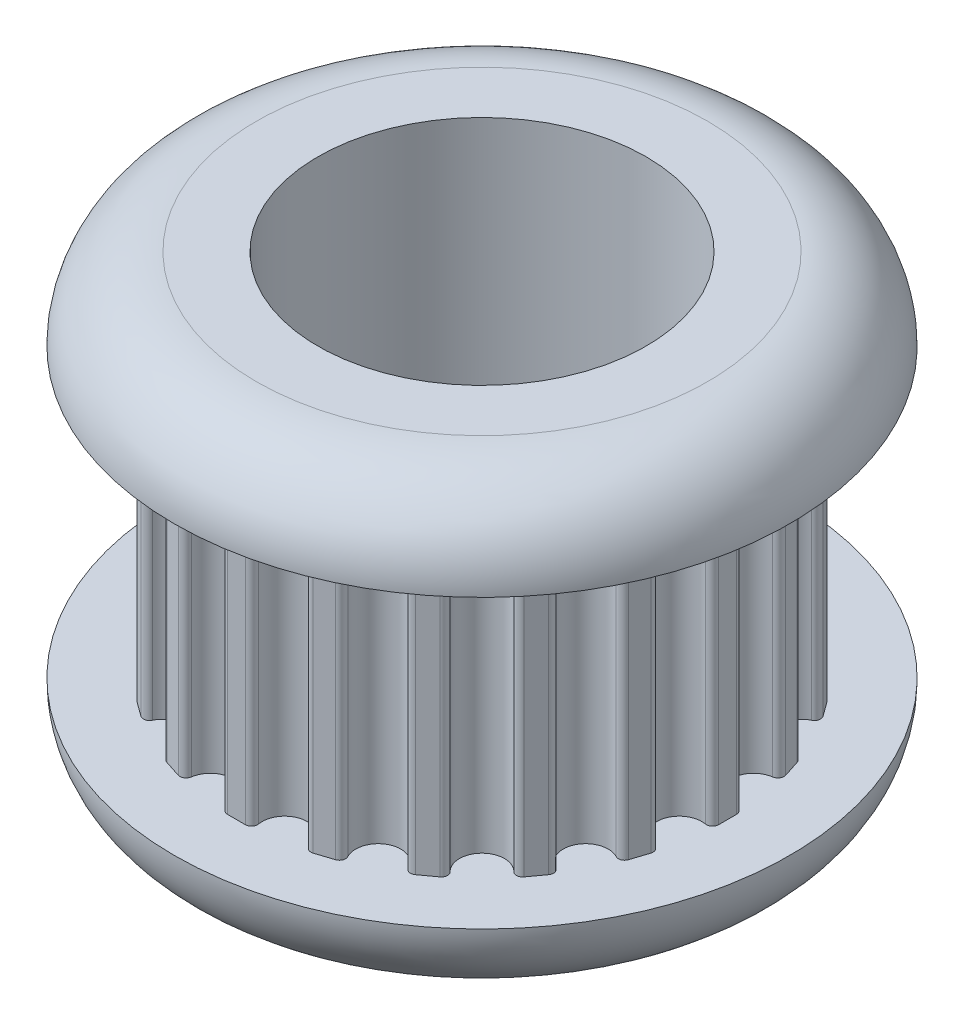
SolidWorks part; units mm, degrees
ref_plane "Front Plane" through (0, 0, 0) normal (0, 0, 1) x (1, 0, 0)
ref_plane "Top Plane" through (0, 0, 0) normal (0, 1, 0) x (1, 0, 0)
ref_plane "Right Plane" through (0, 0, 0) normal (1, 0, 0) x (0, 0, -1)
sketch "Sketch1" plane through (0, 0, 0) normal (0, 1, 0) x (1, 0, 0)
  circle A0 centre (0, 0) radius 6.365
  dimension "D1" = 12.73
extrude "Boss-Extrude2" add sketch "Sketch1" along normal blind 7
sketch "Sketch2" plane through (0, 7, 0) normal (0, 1, 0) x (1, 0, 0)
  line L0 (0, 0) -> (0, 6.365) construction
  line L1 (0, 5.985) -> (0.2155, 5.985)
  line L2 (0, 5.985) -> (0, 6.365)
  line L3 (0, 0) -> (0.905, 5.7138) construction
  line L4 (0, 6.365) -> (0.8189, 6.365)
  line L5 (1.8495, 5.6921) -> (1.6445, 5.7587)
  line L6 (1.8495, 5.6921) -> (1.9669, 6.0535)
  line L7 (1.9669, 6.0535) -> (1.188, 6.3065)
  line L8 (0.8189, 6.365) -> (1.188, 6.3065)
  circle A0 centre (0, 0) radius 6.365 construction
  arc A1 (0.2155, 5.985) -> (0.3633, 5.809) centre (0.2155, 5.835) cw
  arc A2 (0.3633, 5.809) -> (1.4496, 5.637) centre (0.905, 5.7138) ccw
  arc A3 (1.6445, 5.7587) -> (1.4496, 5.637) centre (1.5981, 5.616) ccw
  dimension "D1" = 0.15
  dimension "D2" = 0.55
  dimension "D3" = 0.38
  dimension "D5" = 9
extrude "Cut-Extrude1" cut sketch "Sketch2" against normal blind 7
pattern_circular "CirPattern1" count 20 over 360 about axis through (0, 7, 0) along (0, 1, 0) of "Cut-Extrude1"
sketch "Sketch3" plane through (0, 7, 0) normal (0, 1, 0) x (1, 0, 0)
  circle A0 centre (0, 0) radius 7.5
extrude "Boss-Extrude3" add sketch "Sketch3" along normal blind 2
fillet "Fillet1" radius 2 1 edges at (0, 9, 7.5)
sketch "Sketch4" plane through (0, 0, 0) normal (0, -1, 0) x (1, 0, 0)
  circle A0 centre (0, 0) radius 7.5
extrude "Boss-Extrude4" add sketch "Sketch4" along normal blind 2
fillet "Fillet2" radius 2 1 edges at (0, -2, -7.5)
sketch "Sketch5" plane through (0, -2, 0) normal (0, -1, 0) x (1, 0, 0)
  circle A0 centre (0, 0) radius 4
extrude "Cut-Extrude2" cut sketch "Sketch5" against normal through all
equation "\"n\"= 20"
equation "\"p\"= 2"
equation "\"pd\"= \"n\" * \"p\" / pi"
